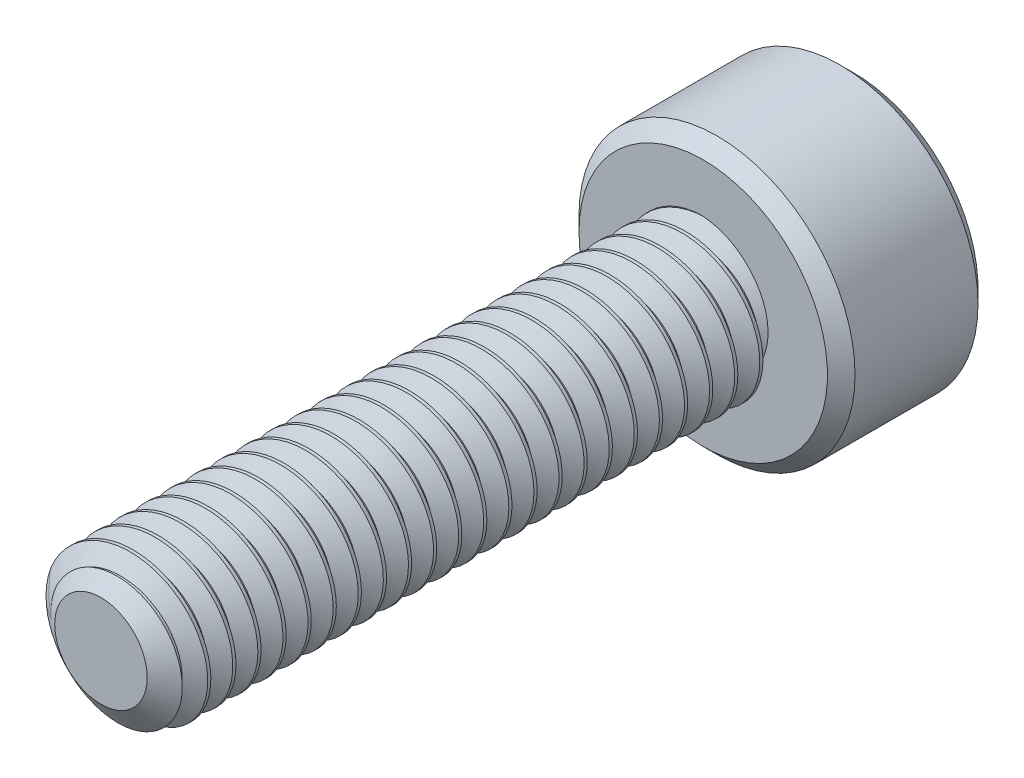
SolidWorks part; units mm, degrees
other "DetailItem1"
ref_plane "Front Plane" through (0, 0, 0) normal (0, 0, 1) x (1, 0, 0)
ref_plane "Top Plane" through (0, 0, 0) normal (0, 1, 0) x (1, 0, 0)
ref_plane "Right Plane" through (0, 0, 0) normal (1, 0, 0) x (0, 0, -1)
sketch "Sketch1" plane through (0, 0, 0) normal (0, 0, 1) x (1, 0, 0)
  circle A0 centre (0, 0) radius 1.5
  dimension "OD" = 3
extrude "Extrude1" add sketch "Sketch1" against normal blind 12
sketch "Sketch2" plane through (0, 0, 0) normal (0, 0, 1) x (1, 0, 0)
  circle A0 centre (0, 0) radius 1.5 construction
  circle A1 centre (0, 0) radius 1.5
curve "Helix/Spiral1" pitch 0.5 height 12.5 radius 1.5 centre (0, 0, 0) axis (0, 0, -1) start towards (0, 1, 0) parameters "pitch"=0.5
sketch "Sketch3" plane through (0, 0, 0) normal (1, 0, 0) x (0, 0, -1)
  line L0 (-0.4375, 1.5) -> (-0.25, 1.1752)
  line L1 (-0.25, 1.1752) -> (-0.1875, 1.1752)
  line L2 (-0.1875, 1.1752) -> (0, 1.5)
  line L3 (-0.4375, 1.5) -> (0, 1.5)
  line L4 (-0.2187, 1.5) -> (-0.2188, 1.1752) construction
  line L5 (-0.3438, 1.3376) -> (-0.0938, 1.3376) construction
  line L6 (0, 1.5) -> (0, -1.5) construction
  dimension "D1" = 0.0625
  dimension "D2" = 0.25
  dimension "D3" = 60
sweep "Cut-Sweep1" cut profiles "Sketch3" path "Helix/Spiral1" align with end faces yes
sketch "Sketch4" plane through (0, 0, 0) normal (1, 0, 0) x (0, 0, -1)
  line L0 (0.4053, 1.5) -> (0, 0.9212)
  line L1 (0, 0.9212) -> (0, 1.5)
  line L2 (0.4053, 1.5) -> (0, 1.5)
  line L3 (-0.4375, 1.5) -> (0, 1.5) construction
  line L4 (0, 0) -> (7.0209, 0) construction
  dimension "D1" = 55
  dimension "D2" = 0.254
revolve "Cut-Revolve1" cut sketch "Sketch4" angle 360 about L4
sketch "Sketch6" plane through (0, 0, -12) normal (0, 0, -1) x (-1, 0, 0)
  circle A0 centre (0, 0) radius 2.75
  dimension "head dia" = 5.5
extrude "Extrude2" add sketch "Sketch6" along normal blind 3
sketch "Sketch7" plane through (0, 0, -15) normal (0, 0, -1) x (-1, 0, 0)
  line L1 (0, 1.4434) -> (-1.25, 0.7217)
  line L2 (-1.25, 0.7217) -> (-1.25, -0.7217)
  line L3 (-1.25, -0.7217) -> (0, -1.4434)
  line L4 (0, -1.4434) -> (1.25, -0.7217)
  line L5 (1.25, -0.7217) -> (1.25, 0.7217)
  line L6 (1.25, 0.7217) -> (0, 1.4434)
  circle A0 centre (0, 0) radius 1.25 construction
  dimension "hex dia" = 2.5
extrude "Cut-Extrude1" cut sketch "Sketch7" against normal blind 1.875
sketch "Sketch8" plane through (0, 0, -15) normal (0, 0, -1) x (-1, 0, 0)
  circle A0 centre (0, 0) radius 1.4434
extrude "Cut-Extrude2" cut sketch "Sketch8" against normal through all draft 45
chamfer "Chamfer1" distance 0.275 angle 45 2 edges at (-2.75, 0, -15) (-2.75, 0, -12)
sketch "Sketch10" plane through (0, 0, -12) normal (0, 0, 1) x (1, 0, 0)
  circle A1 centre (0, 0) radius 1.5
  circle A2 centre (0, 0) radius 1.5
  dimension "D1" = 0
ref_plane "Plane1" through (0, 0, 0) normal (0, 0, 1) x (1, 0, 0)
extrude "partial thread" [suppressed] add sketch "Sketch10" along normal up to surface (4 mm away) separate body
chamfer "Chamfer2" [suppressed] distance 0.06 angle 45
combine bodies "Combine1" [suppressed] operation type add bodies to combine 107 108
sketch "Sketch9" plane through (0, 0, 0) normal (1, 0, 0) x (0, 0, -1)
  line L0 (0, 1.5) -> (0, -1.5) construction
  line L1 (1.25, 1.5) -> (1.25, -1.5) construction
  dimension "D1" = 1.25
equation "\"D3@Helix/Spiral1\" = \"screw length@Extrude1\"+\"pitch@Helix/Spiral1\""
equation "\"D1@Sketch3\" = \"pitch@Helix/Spiral1\"*.125"
equation "\"D2@Sketch3\" = \"pitch@Helix/Spiral1\"*.5"
equation "\"D1@Cut-Extrude1\" = \"hex dia@Sketch7\"*.75"
equation "\"D1@Chamfer1\" = \"head dia@Sketch6\"*.05"
equation "\"D1@Sketch9\" = \"pitch@Helix/Spiral1\"*2.5"
equation "\"D1@Chamfer2\"=\"OD@Sketch1\"*.02"
